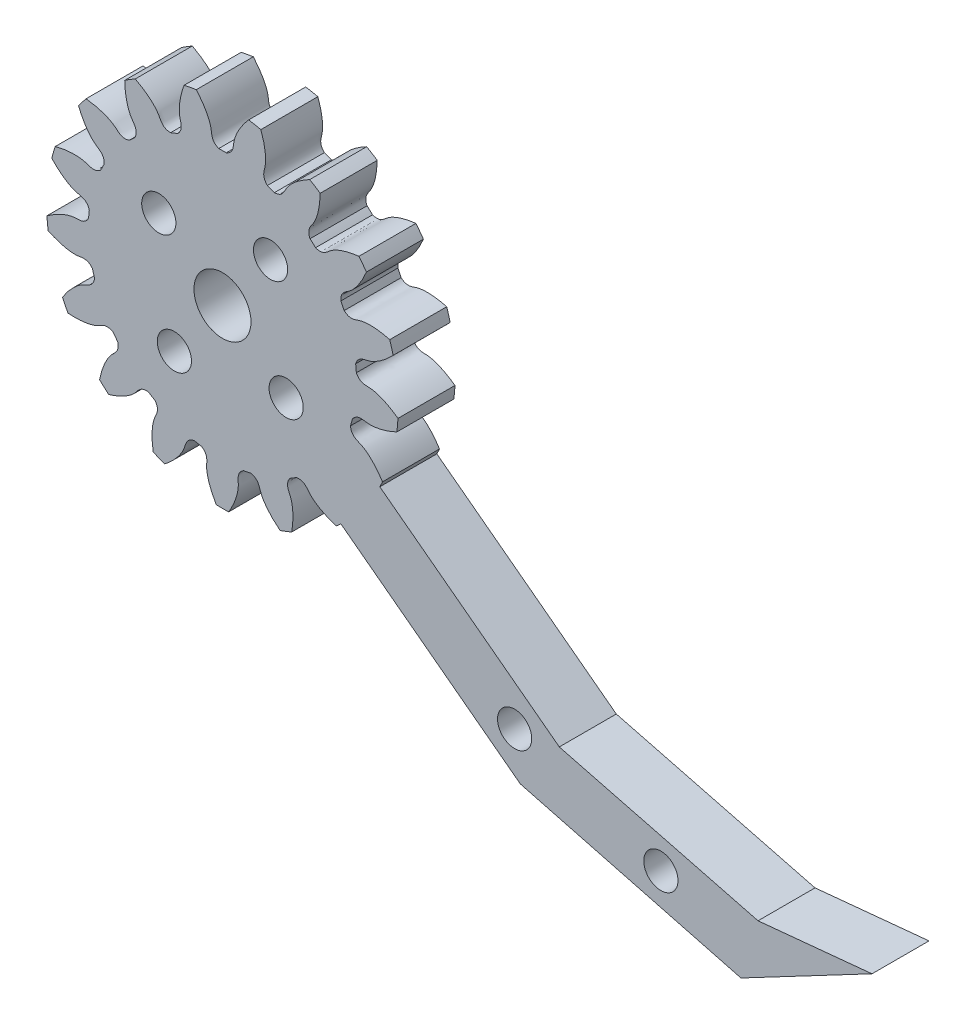
SolidWorks part; units mm, degrees
material "45"
ref_plane "前视基准面" through (0, 0, 0) normal (0, 0, 1) x (1, 0, 0)
ref_plane "上视基准面" through (0, 0, 0) normal (0, 1, 0) x (1, 0, 0)
ref_plane "右视基准面" through (0, 0, 0) normal (1, 0, 0) x (0, 0, -1)
sketch "草图1" plane through (0, 0, 0) normal (0, 0, 1) x (1, 0, 0)
  circle A0 centre (0, 0) radius 15.4185
extrude "凸台-拉伸1" add sketch "草图1" along normal blind 5
ref_axis "基准轴1" through (0, 0, 5) along (0, 0, -1)
sketch "草图2" plane through (0, 0, 0) normal (0, 0, 1) x (1, 0, 0)
  line L0 (0, 0) -> (0, 15.4185) construction
  arc A0 (0.3273, 11.7622) -> (-0.3273, 11.7622) centre (0, 0) ccw
  arc A1 (5.0567, 17.4322) -> (-5.0567, 17.4322) centre (0, 0) ccw
  spline S0 degree 3 poles (0.3273, 11.7622) (1.019, 12.0505) (0.9189, 12.5861) (1.036, 13.0892) (1.0468, 13.1319) (1.0598, 13.1794) (1.0753, 13.2316) (1.0934, 13.2885) (1.1143, 13.3498) (1.1382, 13.4156) (1.1652, 13.4858) (1.1956, 13.5602) (1.2296, 13.6388) (1.2672, 13.7213) (1.3088, 13.8078) (1.3544, 13.898) (1.4042, 13.9919) (1.4584, 14.0894) (1.5172, 14.1902) (1.5807, 14.2942) (1.649, 14.4013) (1.7223, 14.5113) (1.8008, 14.6242) (1.8846, 14.7396) (1.9737, 14.8574) (2.0685, 14.9775) (2.1689, 15.0997) (2.2751, 15.2239) (2.3872, 15.3497) (2.5053, 15.4771) (2.6296, 15.6058) (2.7601, 15.7356) (2.8969, 15.8665) (3.0401, 15.998) (3.1898, 16.1301) (3.346, 16.2625) (3.5089, 16.3951) (3.6785, 16.5276) (3.8549, 16.6597) (4.0381, 16.7913) (4.2282, 16.9222) (4.4251, 17.0521) (4.6999, 17.2256) (4.9121, 17.3507) (5.0567, 17.4322) knots 0 0 0 0 0.193883 0.199024 0.204851 0.211363 0.21856 0.226443 0.235011 0.244265 0.254205 0.264829 0.27614 0.288136 0.300817 0.314184 0.328236 0.342973 0.358397 0.374505 0.391299 0.408779 0.426944 0.445795 0.465331 0.485552 0.506459 0.528051 0.550329 0.573293 0.596941 0.621276 0.646296 0.672001 0.698392 0.725468 0.753229 0.781677 0.810809 0.840627 0.871131 0.90232 0.934195 1 1 1 1
  spline S1 degree 3 poles (-0.3273, 11.7622) (-1.019, 12.0505) (-0.9189, 12.5861) (-1.036, 13.0892) (-1.0468, 13.1319) (-1.0598, 13.1794) (-1.0753, 13.2316) (-1.0934, 13.2885) (-1.1143, 13.3498) (-1.1382, 13.4156) (-1.1652, 13.4858) (-1.1956, 13.5602) (-1.2296, 13.6388) (-1.2672, 13.7213) (-1.3088, 13.8078) (-1.3544, 13.898) (-1.4042, 13.9919) (-1.4584, 14.0894) (-1.5172, 14.1902) (-1.5807, 14.2942) (-1.649, 14.4013) (-1.7223, 14.5113) (-1.8008, 14.6242) (-1.8846, 14.7396) (-1.9737, 14.8574) (-2.0685, 14.9775) (-2.1689, 15.0997) (-2.2751, 15.2239) (-2.3872, 15.3497) (-2.5053, 15.4771) (-2.6296, 15.6058) (-2.7601, 15.7356) (-2.8969, 15.8665) (-3.0401, 15.998) (-3.1898, 16.1301) (-3.346, 16.2625) (-3.5089, 16.3951) (-3.6785, 16.5276) (-3.8549, 16.6597) (-4.0381, 16.7913) (-4.2282, 16.9222) (-4.4251, 17.0521) (-4.6999, 17.2256) (-4.9121, 17.3507) (-5.0567, 17.4322) knots 0 0 0 0 0.193883 0.199024 0.204851 0.211363 0.21856 0.226443 0.235011 0.244265 0.254205 0.264829 0.27614 0.288136 0.300817 0.314184 0.328236 0.342973 0.358397 0.374505 0.391299 0.408779 0.426944 0.445795 0.465331 0.485552 0.506459 0.528051 0.550329 0.573293 0.596941 0.621276 0.646296 0.672001 0.698392 0.725468 0.753229 0.781677 0.810809 0.840627 0.871131 0.90232 0.934195 1 1 1 1
extrude "切除-拉伸1" cut sketch "草图2" along normal through all
pattern_circular "阵列(圆周)1" count 17 every 21.176 about axis through (0, 0, 5) along (0, 0, -1) of "切除-拉伸1"
sketch "草图3" plane through (0, 0, 0) normal (0, 0, 1) x (1, 0, 0)
  circle A0 centre (0, 0) radius 13.7955 construction
  dimension "Dn" = 27.591
sketch "草图4" plane through (0, 0, 5) normal (0, 0, 1) x (1, 0, 0)
  line L0 (-12.3042, 9.2917) -> (0, 0) construction
  circle A0 centre (0, 0) radius 2.5
  circle A1 centre (0, 0) radius 13.7955 construction
  circle A2 centre (-5.5861, 4.2184) radius 1.5
  arc A4 (-11.9682, 9.7207) -> (-12.6249, 8.8511) centre (0, 0) ccw construction
  circle A5 centre (4.2184, 5.5861) radius 1.5
  circle A6 centre (5.5861, -4.2184) radius 1.5
  circle A7 centre (-4.2184, -5.5861) radius 1.5
  point P19 (0, 0)
  dimension "D1" = 5
  dimension "D2" = 3
  dimension "D3" = 7
  dimension "D4" = 4
extrude "切除-拉伸2" cut sketch "草图4" against normal blind 10
sketch "草图5" plane through (0, 0, 5) normal (0, 0, 1) x (1, 0, 0)
  line L0 (10.3874, -11.3944) -> (26.1316, -23.2839)
  line L1 (13.8021, -6.8726) -> (29.5463, -18.7621)
  line L2 (-12.3042, 9.2917) -> (0, 0) construction
  line L3 (29.5463, -18.7621) -> (46.9769, -23.2537)
  line L4 (46.9769, -23.2537) -> (56.9769, -22.282)
  line L5 (45.4795, -28.3492) -> (56.9769, -22.282)
  line L6 (26.1316, -23.2839) -> (45.4795, -28.3492)
  line L7 (10.3874, -11.3944) -> (6.9653, -7.4401)
  line L8 (6.9653, -7.4401) -> (8.6763, -4.1901)
  line L9 (8.6763, -4.1901) -> (13.8021, -6.8726)
  arc A0 (9.9782, -11.7544) -> (10.7836, -11.0202) centre (0, 0) ccw construction
  arc A1 (13.5506, -7.3561) -> (14.0363, -6.3806) centre (0, 0) ccw construction
  dimension "D1" = 160
  dimension "D2" = 5.6663
  dimension "D3" = 0.221
  dimension "D4" = 35
  dimension "D5" = 35
  dimension "D6" = 18
  dimension "D7" = 20
  dimension "D8" = 10
  dimension "D9" = 13
extrude "凸台-拉伸2" add sketch "草图5" against normal blind 5
sketch "草图6" plane through (0, 0, 5) normal (0, 0, 1) x (1, 0, 0)
  circle A0 centre (38.4557, -23.7171) radius 1.5 construction
  circle A1 centre (25.6281, -19.3495) radius 1.5 construction
  circle A2 centre (38.4557, -23.7171) radius 1.5
  circle A3 centre (25.6281, -19.3495) radius 1.5
extrude "切除-拉伸3" cut sketch "草图6" against normal blind 10
